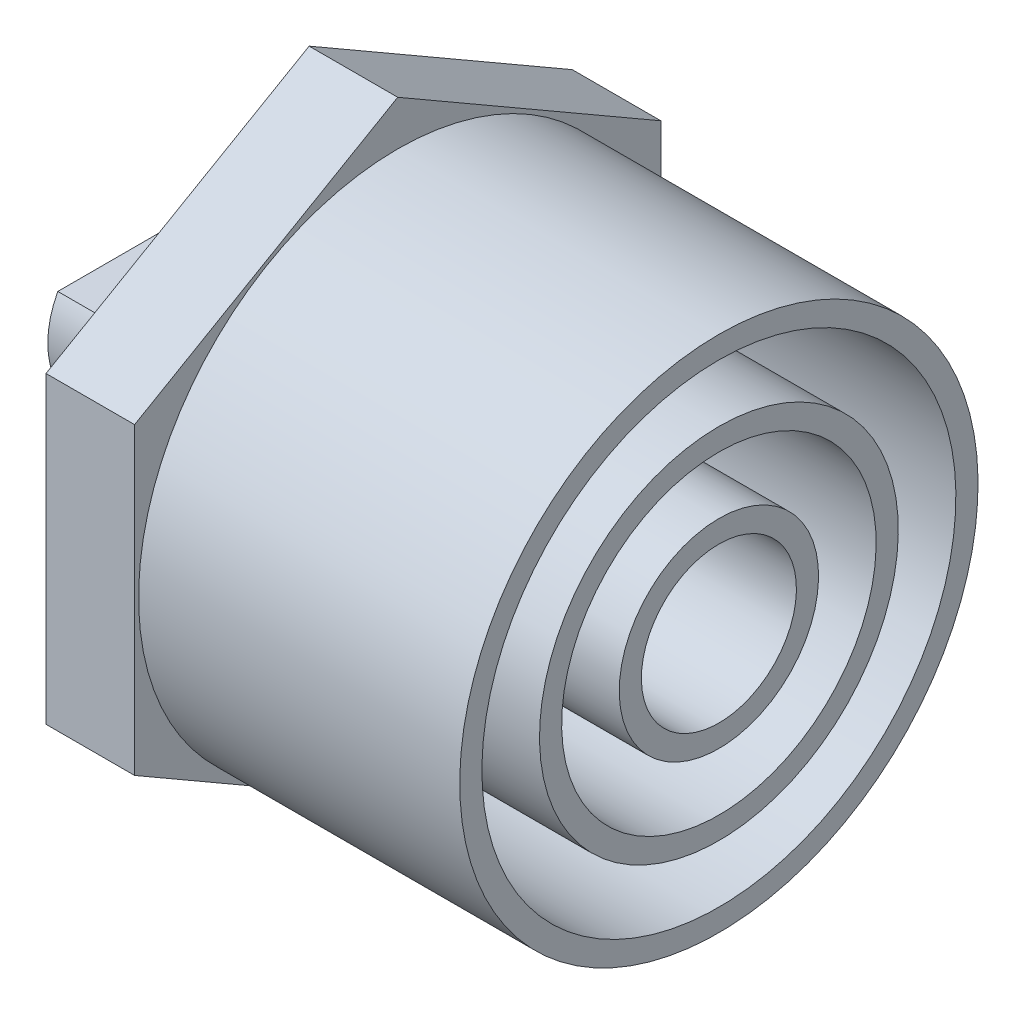
SolidWorks part; units mm, degrees
ref_plane "Front Plane" through (0, 0, 0) normal (0, 0, 1) x (1, 0, 0)
ref_plane "Top Plane" through (0, 0, 0) normal (0, 1, 0) x (1, 0, 0)
ref_plane "Right Plane" through (0, 0, 0) normal (1, 0, 0) x (0, 0, -1)
sketch "Sketch1" plane through (0, 0, 0) normal (0, 0, 1) x (1, 0, 0)
  line L0 (0, 0) -> (0, 5.85)
  line L1 (0, 5.85) -> (8.25, 5.85)
  line L2 (8.25, 5.85) -> (8.25, 5.35)
  line L3 (8.25, 5.35) -> (1, 5.35)
  line L4 (1, 5.35) -> (1, 4.05)
  line L5 (1, 4.05) -> (8.25, 4.05)
  line L6 (8.25, 4.05) -> (8.25, 3.55)
  line L7 (8.25, 3.55) -> (1, 3.55)
  line L9 (1, 0) -> (0, 0)
  line L10 (1, 3.55) -> (1, 2.25)
  line L11 (1, 2.25) -> (8.25, 2.25)
  line L12 (8.25, 2.25) -> (8.25, 1.75)
  line L13 (8.25, 1.75) -> (1, 1.75)
  line L14 (1, 1.75) -> (1, 0)
  dimension "D2" = 1.3
  dimension "D5" = 8.25
  dimension "D4" = 1
  dimension "D3" = 5.85
revolve "Revolve1" add sketch "Sketch1" angle 360 about L9
sketch "Sketch2" plane through (0, 0, 0) normal (-1, 0, 0) x (0, 0, 1)
  line L0 (0, 0) -> (0, 6.8589) construction
  line L1 (0, 6.8589) -> (-5.94, 3.4295)
  line L2 (-5.94, 3.4295) -> (-5.94, -3.4295)
  line L3 (-5.94, -3.4295) -> (0, -6.8589)
  line L4 (0, -6.8589) -> (5.94, -3.4295)
  line L5 (5.94, -3.4295) -> (5.94, 3.4295)
  line L6 (5.94, 3.4295) -> (0, 6.8589)
  circle A0 centre (0, 0) radius 5.94 construction
  circle A1 centre (0, 0) radius 5.85 construction
  circle A2 centre (0, 0) radius 5.85
  circle M8 centre (0, 0) radius 5.85
  dimension "D1" = 11.88
extrude "Boss-Extrude1" add sketch "Sketch2" along normal blind 1 contours L1 L2 L3 L4 L5 L6
extrude "Boss-Extrude2" add sketch "Sketch2<3>" against normal blind 1 contours L5 L6 L1 L2 L3 L4 M8 region at (0, 5.1285, 2.9609)
sketch "Sketch2<3>" plane through (0, 0, 0) normal (-1, 0, 0) x (0, 0, 1) same geometry as "Sketch2"
sketch "Sketch3" plane through (0, 0, 0) normal (0, 0, 1) x (1, 0, 0)
  line L0 (-1, 0) -> (-5, 0) construction
  line L1 (-1, -3.4295) -> (-1, 3.4295) construction
  line L2 (-5, 0.9) -> (-5, -0.9)
  line L3 (-5, -0.9) -> (-1, -0.9)
  line L4 (-1, -0.9) -> (-1, 0.9)
  line L5 (-1, 0.9) -> (-5, 0.9)
  point P8 (-5, 0)
  dimension "D1" = 4
  dimension "D2" = 1.8
extrude "Boss-Extrude3" add sketch "Sketch3" along normal mid plane 3.8
sketch "Sketch4" plane through (-5, 0, 0) normal (-1, 0, 0) x (0, 0, 1)
  line L0 (1.9, 0.9) -> (1.9, -0.9) construction
  line L2 (-1.9, -1.9) -> (1.9, -1.9)
  line L3 (-1.9, -1.9) -> (-1.9, 1.9)
  line L4 (-1.9, 1.9) -> (1.9, 1.9)
  line L5 (1.9, -1.9) -> (1.9, 1.9)
  line L6 (-1.9, -1.9) -> (1.9, 1.9) construction
  line L7 (-1.9, 1.9) -> (1.9, -1.9) construction
  circle A0 centre (0, 0) radius 1.9
  line M2 (-1.9, 0.9) -> (-1.9, -0.9)
  line M3 (-1.9, -0.9) -> (1.9, -0.9)
  line M4 (1.9, -0.9) -> (1.9, 0.9)
  line M5 (1.9, 0.9) -> (-1.9, 0.9)
extrude "Cut-Extrude1" cut sketch "Sketch4" against normal up to surface (4 mm away) contours A0 M5 M2 | A0 L3 M3 | A0 M3 M4 | A0 L5 M5 region at (-5, -0.6778, -1.8328) region at (-5, -0.6778, 1.8328) region at (-5, 0.6778, -1.8328) region at (-5, 0.6778, 1.8328) up to face at (-1, 0, 0)
equation "\"w\"= 0.5mm"
equation "\"D1@Sketch1\"=\"w\""
equation "\"delta\"= 0.4mm"
equation "\"D2@Sketch1\"=\"w\" + 2*\"delta\""
equation "\"D4@Sketch1\"=\"w\"*2"
equation "\"D1@Sketch2\"=2*5.94"
